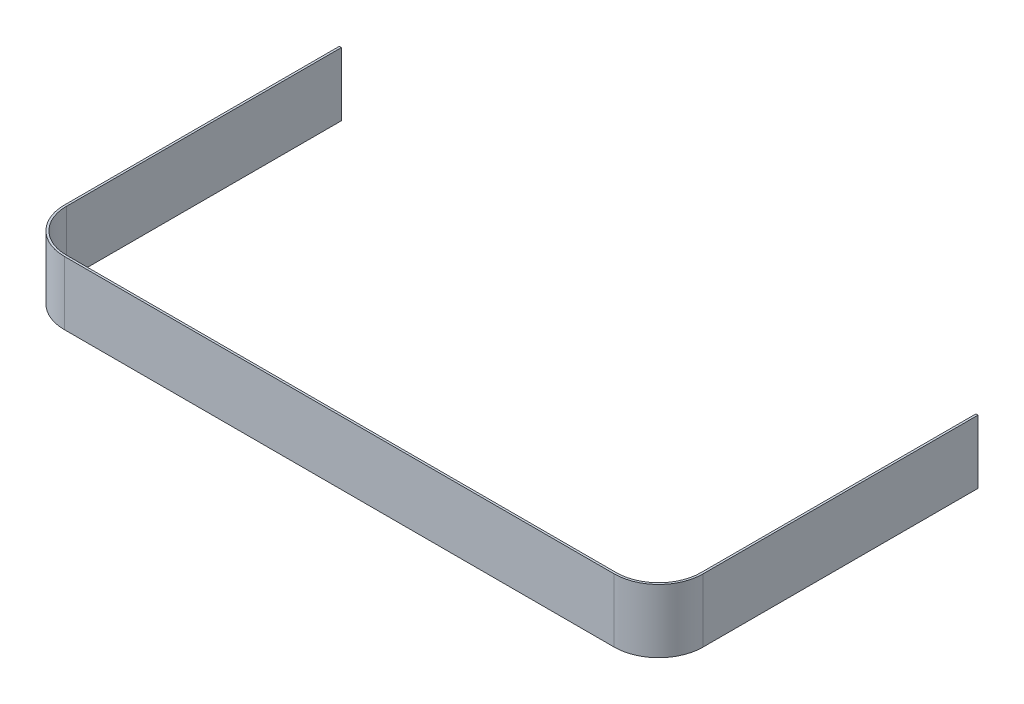
SolidWorks part; units mm, degrees
ref_plane "Ebene vorne" through (0, 0, 0) normal (0, 0, 1) x (1, 0, 0)
ref_plane "Ebene oben" through (0, 0, 0) normal (0, 1, 0) x (1, 0, 0)
ref_plane "Ebene rechts" through (0, 0, 0) normal (1, 0, 0) x (0, 0, -1)
sketch "Skizze1" plane through (0, 0, 0) normal (0, -1, 0) x (1, 0, 0)
  line L0 (0, 75) -> (130, 75)
  line L1 (-130, 75) -> (130, 75) construction
  line L2 (150, 55) -> (150, -75)
  arc A0 (130, 75) -> (150, 55) centre (130, 55) cw
extrude "Linear-Austragen-Dünn1" add sketch "Skizze1" against normal blind 30 thin thin type one direction reverse wall 1
mirror "Spiegeln1" about plane through (0, 30, 75) normal (1, 0, 0) of "Linear-Austragen-Dünn1"
